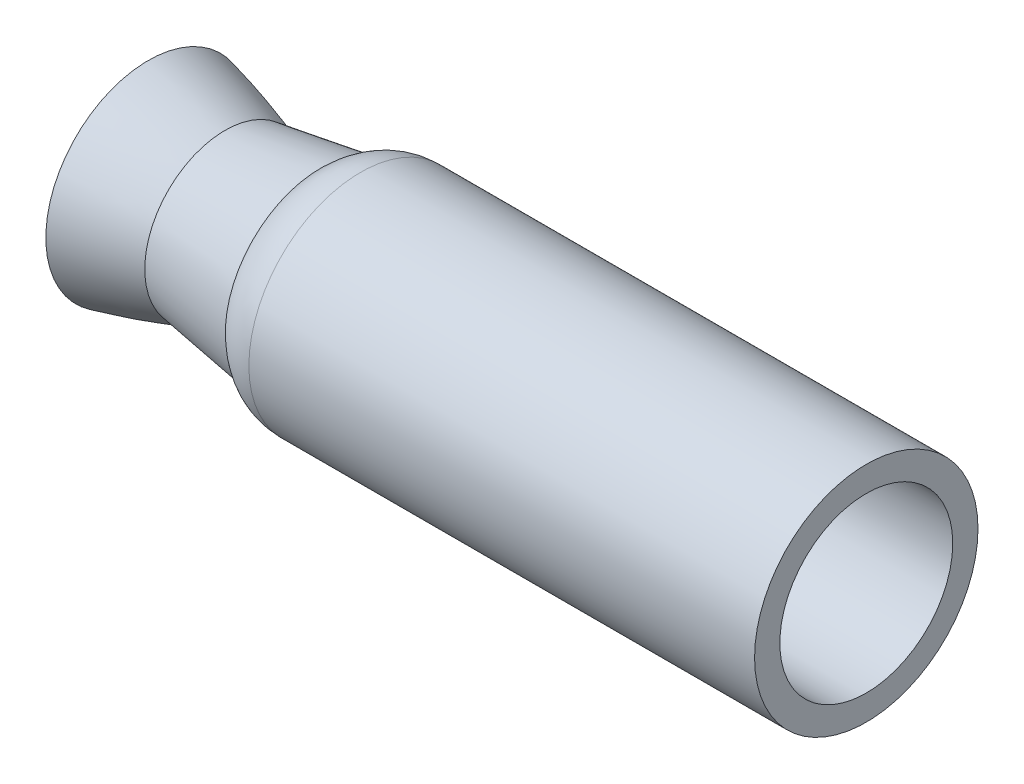
SolidWorks part; units mm, degrees
material "Thornel Mat VMA"
ref_plane "Front Plane" through (0, 0, 0) normal (0, 0, 1) x (1, 0, 0)
ref_plane "Top Plane" through (0, 0, 0) normal (0, 1, 0) x (1, 0, 0)
ref_plane "Right Plane" through (0, 0, 0) normal (1, 0, 0) x (0, 0, -1)
sketch "Sketch1" plane through (0, 0, 0) normal (0, 0, 1) x (1, 0, 0)
  line L0 (189.133, 27.386) -> (28.9492, 27.386)
  line L1 (21.8782, 24.4571) -> (13.5417, 16.1206)
  line L3 (0, 0) -> (-234.9488, 0) construction
  line L5 (16.2213, 30.1139) -> (-13.9816, 25.4377)
  line L8 (189.133, 35.386) -> (28.9492, 35.386)
  line L12 (16.2213, 30.1139) -> (7.8848, 21.7775)
  line L13 (189.133, 27.386) -> (189.133, 35.386)
  line L14 (-40.127, 24.64) -> (-38.315, 32.4321)
  arc A0 (28.9492, 27.386) -> (21.8782, 24.4571) centre (28.9492, 17.386) ccw
  arc A4 (28.9492, 35.386) -> (16.2213, 30.1139) centre (28.9492, 17.386) ccw
  arc A7 (2.3482, 19.2268) -> (2.3482, 19.2268) centre (2.3482, 19.2268) cw
  arc A8 (7.8848, 21.7775) -> (2.3482, 19.2268) centre (1.6623, 28) cw construction
  arc A9 (2.3482, 19.2268) -> (7.8848, 21.7775) centre (1.6623, 28) ccw
  arc A10 (0.1069, 11.2722) -> (0, 11.5361) centre (3.1693, 12.6659) cw construction
  arc A11 (13.5417, 16.1206) -> (0.1069, 11.2722) centre (1.6623, 28) cw construction
  arc A12 (13.5417, 16.1206) -> (1.6623, 11.2) centre (1.6623, 28) cw
  arc A13 (1.6623, 11.2) -> (0, 11.5361) centre (1.6623, 15.4784) cw
  spline S0 degree 2 poles (0, 11.5361) (-19.9483, 19.9476) (-40.127, 24.64) knots 0 0 0 1 1 1 construction
  spline S1 degree 1 poles (2.3482, 19.2268) (-38.315, 32.4321) knots 0 0 1 1 construction
  spline S2 degree 2 poles (0, 11.5361) (-19.9483, 19.9476) (-40.127, 24.64) knots 0 0 0 1 1 1
  spline S3 degree 2 poles (2.3482, 19.2268) (0.3135, 20.0775) (-5.8003, 22.5182) (-13.9784, 25.475) (-28.1602, 30.0701) (-38.315, 32.4321) knots 0.018494 0.018494 0.018494 0.117488 0.315475 0.513463 1 1 1
  dimension "D1" = 10
  dimension "D4" = 16.8
  dimension "D5" = 4.2784
  dimension "D14" = 27.386
  dimension "D16" = 167.2548
  dimension "D2" = 11.2
  dimension "D6" = 45
  dimension "D7" = 24.64
  dimension "D3" = 8
revolve "Revolve1" add sketch "Sketch1" angle 360 about L3 region at (72.719, 28.6368, 0) region at (2.2964, 24.7796, 0)
equation "\"theta_t\"= 36.9009 - ( 426.271 / ( \"Aet\" + 7.00037 ) ) + ( 10026.8 / ( \"Aet\" + 7.00037 ) ^ 2 ) - ( 175410 / ( \"Aet\" + 7.00037 ) ^ 3 ) + ( ( 1.6742 * ( 10 ^ 6 ) ) / ( \"Aet\" + 7.00037 ) ^ 4 ) - ( ( 6.7643 * ( 10 ^ 6 ) ) / ( \"Aet\" + 7.00037 ) ^ 5 )"
equation "\"rt\"= 11.2"
equation "\"re\"= sqr ( \"rt\" ^ 2 * \"Aet\" )"
equation "\"Aet\"= 4.84"
equation "\"L\"= 0.8 * ( ( \"re\" / tan ( 15 ) ) - ( \"rt\" / tan ( 15 ) ) )"
equation "\"lc\"= ( \"l*\" / \"cr\" )"
equation "\"b\"= tan ( \"theta_t\" )"
equation "\"a\"= ( \"re\" - \"b\" * \"L\" - \"c\" ) / \"L\" ^ 2"
equation "\"c\"= \"rt\" * ( 1.382 - 0.382 * cos ( \"theta_t\" ) )"
equation "\"cr\"= 5.9789"
equation "\"rc\"= sqr ( \"cr\" * ( \"rt\" ^ 2 ) )"
equation "\"D14@Sketch1\"=\"rc\""
equation "\"l*\"= 1000"
equation "\"D16@Sketch1\"=\"lc\""
equation "\"th\"= 8"
equation "\"theta_cr\"= 45deg"
equation "\"theta_e\"= 5.48 + ( 134.316 / ( \"Aet\" + 1.49269 ) ) - ( 1742.02 / ( \"Aet\" + 1.49269 ) ^ 2 ) + ( 13091 / ( \"Aet\" + 1.49269 ) ^ 3 ) - ( 41929.9 / ( \"Aet\" + 1.49269 ) ^ 4 ) + ( 44445.1 / ( \"Aet\" + 1.49269 ) ^ 5 )"
equation "\"Nx\"= 0"
equation "\"Ny\"= \"c\""
equation "\"Qx\"= ( \"re\" - ( tan ( \"theta_e\" ) * \"L\" ) - \"c\" ) / ( tan ( \"theta_t\" ) - tan ( \"theta_e\" ) )"
equation "\"Qy\"= tan ( \"theta_t\" ) * \"Qx\" + \"c\""
equation "\"Ex\"= \"L\""
equation "\"Ey\"= \"re\""
equation "\"D3@Sketch1\"=\"th\""
equation "\"D2@Sketch1\"=\"rt\""
equation "\"D4@Sketch1\"=\"rt\"*1.5"
equation "\"D5@Sketch1\"=\"rt\"*0.382"
equation "\"D6@Sketch1\"=\"theta_cr\""
equation "\"D7@Sketch1\"=\"re\""
